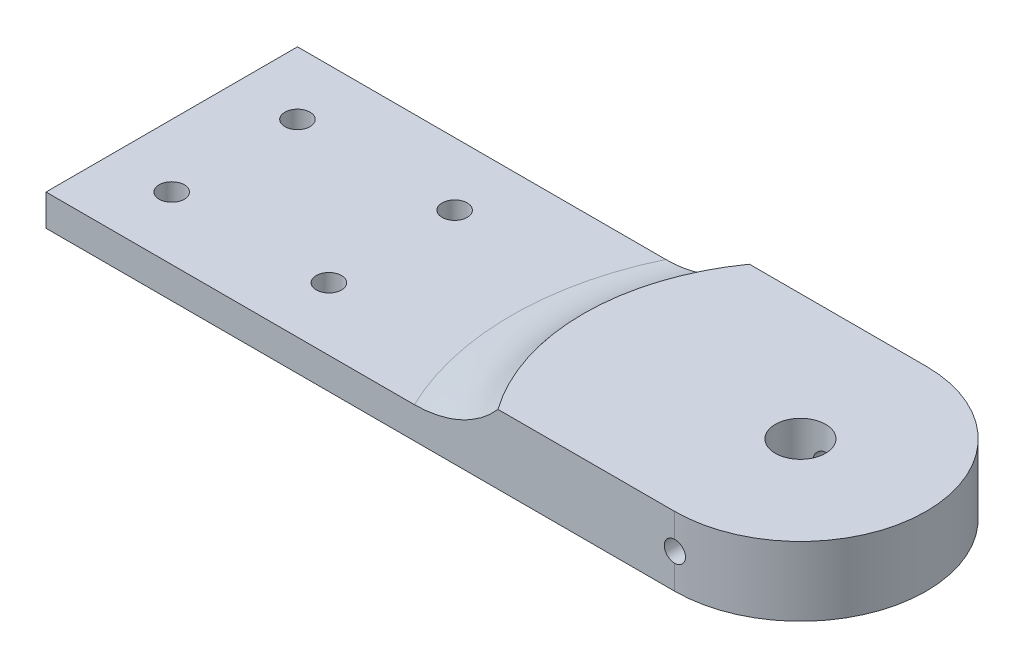
SolidWorks part; units mm, degrees
material "1060 Alloy"
ref_plane "Front Plane" through (0, 0, 0) normal (0, 0, 1) x (1, 0, 0)
ref_plane "Top Plane" through (0, 0, 0) normal (0, 1, 0) x (1, 0, 0)
ref_plane "Right Plane" through (0, 0, 0) normal (1, 0, 0) x (0, 0, -1)
sketch "Sketch1" plane through (0, 0, 0) normal (0, 1, 0) x (1, 0, 0)
  line L0 (-100, 20) -> (20, 20)
  line L1 (20, 20) -> (20, -5)
  line L2 (20, -5) -> (-100, -5) construction
  line L3 (-100, -5) -> (-100, 20)
  line L4 (20, -5) -> (20, -20)
  line L5 (20, -20) -> (-100, -20)
  line L6 (-100, -20) -> (-100, -5)
  line L7 (20, -10) -> (-90, -10) construction
  line L8 (-90, -10) -> (-90, -5) construction
  line L9 (-90, -5) -> (-90, 10) construction
  line L10 (-90, 10) -> (20, 10) construction
  circle A0 centre (0, 0) radius 4
  circle A1 centre (-90, 10) radius 2
  circle A2 centre (-65, 10) radius 2
  circle A3 centre (-65, -10) radius 2
  circle A4 centre (-90, -10) radius 2
  arc A5 (0, -20) -> (0, 20) centre (0, 0) ccw
  dimension "D1" = 8
  dimension "D7" = 4
  dimension "D2" = 20
  dimension "D3" = 25
  dimension "D4" = 20
  dimension "D5" = 15
  dimension "D6" = 120
  dimension "D9" = 25
  dimension "D8" = 10
extrude "Boss-Extrude1" add sketch "Sketch1" along normal blind 11 contours L5 A5 L0 L3 L6 A4 A3 A2 A1 A0 region at (-42.1334, 0, 0)
sketch "Sketch4" plane through (0, 11, 0) normal (0, 1, 0) x (1, 0, 0)
  line L0 (-28.1114, 20) -> (-100, 20)
  line L1 (-100, 20) -> (-100, -20)
  line L2 (-100, -20) -> (-28.1114, -20)
  arc A1 (-28.1114, 20) -> (-28.1114, -20) centre (0, 0) ccw
  dimension "D1" = 69
extrude "Cut-Extrude1" cut sketch "Sketch4" against normal offset from surface (6 mm away) 5 up to face at (-90, 0, 12)
fillet "Fillet2" radius 14 1 edges at (-34.5, 5, 0)
hole_wizard "M4 Tapped Hole1" positions "Sketch2" profile "Sketch3" tap size "M4" standard "ISO" end condition through all
sketch "Sketch2" plane through (0, 0, -20) normal (0, 0, -1) x (-1, 0, 0)
  line L0 (0, 6.05) -> (0, -6.05) construction
  line L1 (0, 11) -> (0, 0) construction
  point P0 (0, 5.5)
  point P11 (0, 5.5)
cosmetic thread "Hole Thread1" parameters "D2"=4
sketch "Sketch3" plane through (0, 5.5, -20) normal (1, 0, 0) x (0, 1, 0)
  line L0 (0, 0) -> (0, 40)
  line L1 (0, 40) -> (1.65, 40)
  line L2 (1.65, 40) -> (1.65, 0)
  line L5 (1.65, 0) -> (0, 0)
  line L11 (0, -6.35) -> (0, 107.95) construction
  dimension "Thru Tap Drill Dia." = 3.3
  dimension "Thru Tap Drill Depth" = 40
